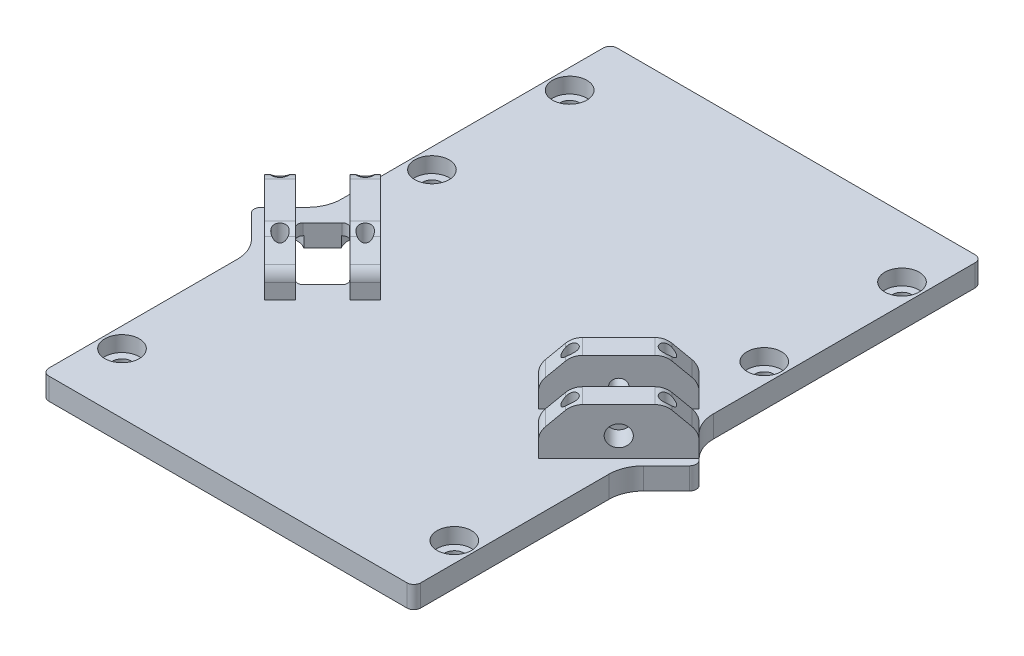
SolidWorks part; units mm, degrees
note: '?' marks a value the reader was unsure of. The reader was unsure of these and kept them because the rebuilt part matched: shared geometry of "Sketch7<3>".
ref_plane "Front Plane" through (0, 0, 0) normal (0, 0, 1) x (1, 0, 0)
ref_plane "Top Plane" through (0, 0, 0) normal (0, 1, 0) x (1, 0, 0)
ref_plane "Right Plane" through (0, 0, 0) normal (1, 0, 0) x (0, 0, -1)
ref_axis "Axis1" through (0, 0, -88.99) along (0, 0, 1)?
ref_axis "Axis2" through (0, -55, 0) along (0, 1, 0)?
ref_axis "Axis3" through (-88.99, 0, 0) along (1, 0, 0)?
sketch "Sketch1" plane through (0, 0, 0) normal (0, 1, 0) x (1, 0, 0)
  line L0 (-52.8995, 10.8995) -> (-33.1005, -8.8995) construction
  line L1 (65, -27.5) -> (-65, -27.5)
  line L2 (65, -27.5) -> (65, 27.5)
  line L3 (65, 27.5) -> (-65, 27.5)
  line L4 (-65, -27.5) -> (-65, 27.5)
  line L5 (65, -27.5) -> (-65, 27.5) construction
  line L6 (65, 27.5) -> (-65, -27.5) construction
  line L7 (-52.8995, 1) -> (-33.1005, 1) construction
  line L8 (-59.0867, 4.7123) -> (-46.7123, 17.0867) construction
  line L9 (-39.2877, -15.0867) -> (-26.9133, -2.7123) construction
  line L10 (-43, 1) -> (-43, -27.5) construction
  point P0 (0, 0)
  point P22 (-43, 1)
  point P25 (-52.8995, 10.8995)
  dimension "D2" = 45
  dimension "D3" = 28
  dimension "D4" = 17.5
  dimension "D5" = 1
  dimension "D6" = 43
  dimension "D7" = 55
  dimension "D8" = 130
extrude "Boss-Extrude1" add sketch "Sketch1" along normal blind 6.35
sketch "Sketch2" plane through (0, 6.35, 0) normal (0, 1, 0) x (1, 0, 0)
  line L0 (-63.0995, 4.235) -> (-39.765, -19.0995)
  line L1 (-39.765, -19.0995) -> (-35.2749, -14.6094)
  line L2 (-35.2749, -14.6094) -> (-58.6094, 8.7251)
  line L3 (-58.6094, 8.7251) -> (-63.0995, 4.235)
  line L4 (-59.0867, 4.7123) -> (-39.2877, -15.0867) construction
  line L5 (-52.8995, 10.8995) -> (-33.1005, -8.8995) construction
  line L6 (-22.9005, -2.235) -> (-27.3906, -6.7251)
  line L7 (-46.235, 21.0995) -> (-22.9005, -2.235)
  line L8 (-50.7251, 16.6094) -> (-46.235, 21.0995)
  line L9 (-27.3906, -6.7251) -> (-50.7251, 16.6094)
  dimension "D1" = 2.5
  dimension "D2" = 2.5
  dimension "D3" = 6.35
extrude "Boss-Extrude2" add sketch "Sketch2" along normal blind 13.5 separate body
hole_wizard "Tap Drill for M5x0.8 Tap1" positions "Sketch5" profile "Sketch4" hole size "M5x0.8" standard "ANSI Metric" end condition through all
sketch "Sketch5" plane through (-29.4322, 0, 29.4322) normal (-0.7071, 0, 0.7071) x (0.7071, 0, 0.7071)
  line L0 (-31.1127, 19.85) -> (-31.1127, 12) construction
  line L1 (-47.6127, 19.85) -> (-14.6127, 19.85) construction
  line L3 (-26.5165, 0) -> (-65.4074, 0) construction
  circle A0 centre (-31.1127, 12) radius 11 construction
  point P0 (-31.1127, 12)
  dimension "D1" = 22
  dimension "D2" = 12
sketch "Sketch4" plane through (-51.4322, 12, 7.4322) normal (0, 1, 0) x (0.7071, 0, 0.7071)
  line L0 (0, 0) -> (0, 107.0309)
  line L1 (0, 107.0309) -> (2.1, 107.0309)
  line L2 (2.1, 107.0309) -> (2.1, 0)
  line L5 (2.1, 0) -> (0, 0)
  line L11 (0, -6.35) -> (0, 107.95) construction
  dimension "Thru Hole Dia." = 4.2
  dimension "Thru Hole Depth" = 107.0309
chamfer "Chamfer1" distance 7 angle 45 2 edges at (-37.5199, 19.85, 16.8544) (-60.8544, 19.85, -6.4801)
fillet "Fillet1" radius 5 4 edges at (-37.5199, 12.85, 16.8544) (-42.4697, 19.85, 11.9047) (-55.9047, 19.85, -1.5303) (-60.8544, 12.85, -6.4801)
chamfer "Chamfer2" distance 7 angle 45 2 edges at (-48.4801, 19.85, -18.8544) (-25.1456, 19.85, 4.4801)
fillet "Fillet2" radius 5 4 edges at (-48.4801, 12.85, -18.8544) (-43.5303, 19.85, -13.9047) (-30.0953, 19.85, -0.4697) (-25.1456, 12.85, 4.4801)
sketch "Sketch6" plane through (0, 6.35, 0) normal (0, 1, 0) x (1, 0, 0)
  line L0 (-53.5978, 3.7135) -> (-40.2865, -9.5978)
  line L1 (-57.5738, 7.6896) -> (-54.6952, 4.8109) construction
  line L2 (-39.1891, -10.6952) -> (-36.3104, -13.5738) construction
  line L3 (-38.0414, -9.5978) -> (-32.4022, -3.9586)
  line L4 (-28.4262, -5.6896) -> (-31.3048, -2.8109) construction
  line L5 (-32.4022, -1.7135) -> (-45.7135, 11.5978)
  line L6 (-46.8109, 12.6952) -> (-49.6896, 15.5738) construction
  line L7 (-47.9586, 11.5978) -> (-53.5978, 5.9586)
  line L8 (-51.4322, -7.4322) -> (-34.5678, 9.4322) construction
  line L9 (-56.6853, -2.1792) -> (-46.1792, -12.6853) construction
  line L10 (-29.3147, 4.1792) -> (-39.8208, 14.6853) construction
  line L11 (0, 0) -> (0, -27.5) construction
  line L12 (-65, -27.5) -> (65, -27.5) construction
  line L13 (47.9586, 11.5978) -> (53.5978, 5.9586)
  line L14 (32.4022, -1.7135) -> (45.7135, 11.5978)
  line L15 (38.0414, -9.5978) -> (32.4022, -3.9586)
  line L16 (53.5978, 3.7135) -> (40.2865, -9.5978)
  arc A0 (-32.4022, -3.9586) -> (-32.4022, -1.7135) centre (-33.5248, -2.8361) ccw
  arc A1 (-40.2865, -9.5978) -> (-38.0414, -9.5978) centre (-39.1639, -8.4752) ccw
  arc A2 (-45.7135, 11.5978) -> (-47.9586, 11.5978) centre (-46.8361, 10.4752) ccw
  arc A3 (-53.5978, 3.7135) -> (-53.5978, 5.9586) centre (-52.4752, 4.8361) cw
  arc A4 (53.5978, 3.7135) -> (53.5978, 5.9586) centre (52.4752, 4.8361) ccw
  arc A5 (45.7135, 11.5978) -> (47.9586, 11.5978) centre (46.8361, 10.4752) cw
  arc A6 (32.4022, -3.9586) -> (32.4022, -1.7135) centre (33.5248, -2.8361) cw
  arc A7 (40.2865, -9.5978) -> (38.0414, -9.5978) centre (39.1639, -8.4752) cw
  point P18 (-46.9421, -2.9421)
  point P21 (-31.2797, -2.8361)
  point P24 (-39.1639, -10.7203)
  point P27 (-46.8361, 12.7203)
  point P30 (-54.7203, 4.8361)
  dimension "D2" = 1.5875
  dimension "D1" = 22
extrude "Cut-Extrude1" cut sketch "Sketch6" against normal through all
hole_wizard "Ø6.0 (6) Diameter Hole1" positions "Sketch11" profile "Sketch10" hole size "Ø6.0" standard "ANSI Metric" end condition through all
sketch "Sketch11" plane through (-29.4322, 0, 29.4322) normal (-0.7071, 0, 0.7071) x (0.7071, 0, 0.7071)
  point P0 (-31.1127, 12)
sketch "Sketch10" plane through (-51.4322, 12, 7.4322) normal (0, 1, 0) x (0.7071, 0, 0.7071)
  line L0 (0, 0) -> (0, 107.0309)
  line L1 (0, 107.0309) -> (3, 107.0309)
  line L2 (3, 107.0309) -> (3, 0)
  line L5 (3, 0) -> (0, 0)
  line L11 (0, -6.35) -> (0, 107.95) construction
  dimension "Thru Hole Dia." = 6
  dimension "Thru Hole Depth" = 107.0309
hole_wizard "Ø3.8 (3.8) Diameter Hole1" positions "Sketch13" profile "Sketch12" hole size "Ø3.8" standard "ANSI Metric" end condition through all
sketch "Sketch13" plane through (0, 0, 0) normal (0, -1, 0) x (-1, 0, 0)
  line L0 (26.9133, -2.7123) -> (46.7123, 17.0867) construction
  line L2 (33.1005, -8.8995) -> (52.8995, 10.8995) construction
  line L4 (43, 1) -> (36.8128, 7.1872) construction
  line L5 (0, 0) -> (0, 27.5) construction
  line L6 (-65, 27.5) -> (65, 27.5) construction
  point P4 (43.8839, 14.2583)
  point P6 (29.7417, 0.1161)
  point P23 (42.1161, -12.2583)
  point P24 (56.2583, 1.8839)
  point P36 (-43.8839, 14.2583)
  point P37 (-56.2583, 1.8839)
  point P38 (-42.1161, -12.2583)
  point P39 (-29.7417, 0.1161)
  dimension "D1" = 20
sketch "Sketch12" plane through (-43.8839, 0, -14.2583) normal (1, 0, 0) x (0, 0, -1)
  line L0 (0, 0) -> (0, 19.85)
  line L1 (0, 19.85) -> (1.9, 19.85)
  line L2 (1.9, 19.85) -> (1.9, 0)
  line L5 (1.9, 0) -> (0, 0)
  line L11 (0, -6.35) -> (0, 107.95) construction
  dimension "Thru Hole Dia." = 3.8
  dimension "Thru Hole Depth" = 19.85
hole_wizard "CBORE for M5 SHCS2" positions "Sketch15" profile "Sketch14" counterbore size "M5" standard "ANSI Metric" end condition through all
sketch "Sketch15" plane through (0, 0, 0) normal (0, -1, 0) x (-1, 0, 0)
  line L0 (0, 0) -> (0, 27.5) construction
  line L1 (-65, 27.5) -> (65, 27.5) construction
  point P0 (29.7417, 0.1161)
  point P3 (43.8839, 14.2583)
  point P6 (42.1161, -12.2583)
  point P9 (56.2583, 1.8839)
  point P19 (-56.2583, 1.8839)
  point P20 (-42.1161, -12.2583)
  point P21 (-43.8839, 14.2583)
  point P22 (-29.7417, 0.1161)
sketch "Sketch14" plane through (-29.7417, 0, -0.1161) normal (1, 0, 0) x (0, 0, -1)
  line L0 (0, 0) -> (0, 19.85)
  line L1 (0, 19.85) -> (2.375, 19.85)
  line L3 (2.375, 19.85) -> (2.375, 3.1)
  line L4 (2.375, 3.1) -> (5, 3.1)
  line L5 (5, 3.1) -> (5, 0)
  line L7 (5, 0) -> (0, 0)
  line L11 (0, -6.35) -> (0, 107.95) construction
  dimension "Thru Hole Dia." = 4.75
  dimension "Thru Hole Depth" = 19.85
  dimension "C'Bore Dia." = 10
  dimension "C'Bore Depth" = 3.1
mirror "Mirror1" about plane through (0, 0, 0) normal (1, 0, 0) of bodies 116 114 105 103
sketch "Sketch7" plane through (0, 6.35, 0) normal (0, 1, 0) x (1, 0, 0)
  line L0 (65, 2.3345) -> (39.8345, 27.5)
  line L1 (65, -27.5) -> (65, 27.5) construction
  line L2 (65, 27.5) -> (-65, 27.5) construction
  line L3 (54, 95.5) -> (54, 13.3345)
  line L4 (54, 95.5) -> (-54, 95.5)
  line L5 (0, 0) -> (0, 95.5) construction
  line L7 (-65, 2.3345) -> (-39.8345, 27.5)
  line L8 (-54, 95.5) -> (-54, 13.3345)
  line L9 (54, -8.6655) -> (65, 2.3345)
  line L11 (65, 27.5) -> (-65, 27.5)
  line L12 (-65, 27.5) -> (-65, -27.5)
  line L13 (-65, -27.5) -> (65, -27.5)
  line L14 (65, -27.5) -> (65, 27.5)
  line L15 (65, 27.5) -> (-65, 27.5)
  line L16 (-65, 27.5) -> (-65, -27.5)
  line L17 (-65, -27.5) -> (65, -27.5)
  line L18 (65, -27.5) -> (65, 27.5)
  line L19 (54, -8.6655) -> (54, -69.5)
  line L20 (54, -69.5) -> (-54, -69.5)
  line L21 (-54, -8.6655) -> (-65, 2.3345)
  line L22 (53.5978, 5.9586) -> (47.9586, 11.5978) construction
  line L23 (-54, -8.6655) -> (-54, -69.5)
  line L24 (35.2749, -14.6094) -> (58.6094, 8.7251) construction
  line L26 (58.6094, 8.7251) -> (63.0995, 4.235) construction
  dimension "D2" = 68
  dimension "D3" = 165
  dimension "D4" = 54
  dimension "D1" = 0
extrude "Boss-Extrude3" add sketch "Sketch7" against normal up to surface (6.35 mm away) up to face at (-43, 0, -1)
extrude "Cut-Extrude2" cut sketch "Sketch7<3>" against normal blind 12.7
sketch "Sketch7<3>" plane through (0, 6.35, 0) normal (0, 1, 0) x (1, 0, 0) same geometry as "Sketch7"
hole_wizard "CBORE for M5 SHCS1" positions "Sketch9" profile "Sketch8" counterbore size "M5" standard "ANSI Metric" end condition through all
sketch "Sketch9" plane through (0, 6.35, 0) normal (0, 1, 0) x (1, 0, 0)
  line L0 (0, 0) -> (0, -69.5) construction
  line L1 (54, -69.5) -> (-54, -69.5) construction
  line L3 (54, 95.5) -> (-54, 95.5) construction
  line L4 (48.25, 38) -> (48.25, -12) construction
  line L5 (48.25, -12) -> (48.25, -52) construction
  point P0 (48.25, 78)
  point P2 (48.25, 38)
  point P18 (-48.25, 38)
  point P19 (-48.25, 78)
  point P20 (48.25, -52)
  point P24 (-48.25, -52)
  dimension "D1" = 96.5
  dimension "D2" = 40
  dimension "D3" = 17.5
  dimension "D4" = 50
  dimension "D5" = 40
sketch "Sketch8" plane through (48.25, 6.35, -78) normal (1, 0, 0) x (0, 0, 1)
  line L0 (0, 0) -> (0, 6.35)
  line L1 (0, 6.35) -> (2.75, 6.35)
  line L3 (2.75, 6.35) -> (2.75, 4.5)
  line L4 (2.75, 4.5) -> (5, 4.5)
  line L5 (5, 4.5) -> (5, 0)
  line L7 (5, 0) -> (0, 0)
  line L11 (0, -6.35) -> (0, 107.95) construction
  dimension "Thru Hole Dia." = 5.5
  dimension "Thru Hole Depth" = 6.35
  dimension "C'Bore Dia." = 10
  dimension "C'Bore Depth" = 4.5
fillet "Fillet3" radius 10 4 edges at (-54, 3.175, -13.3345) (-54, 3.175, 8.6655) (54, 3.175, 8.6655) (54, 3.175, -13.3345)
fillet "Fillet4" radius 2 6 edges at (54, 3.175, -95.5) (-54, 3.175, 69.5) (54, 3.175, 69.5) (65, 3.175, -2.3345) (-54, 3.175, -95.5) (-65, 3.175, -2.3345)
